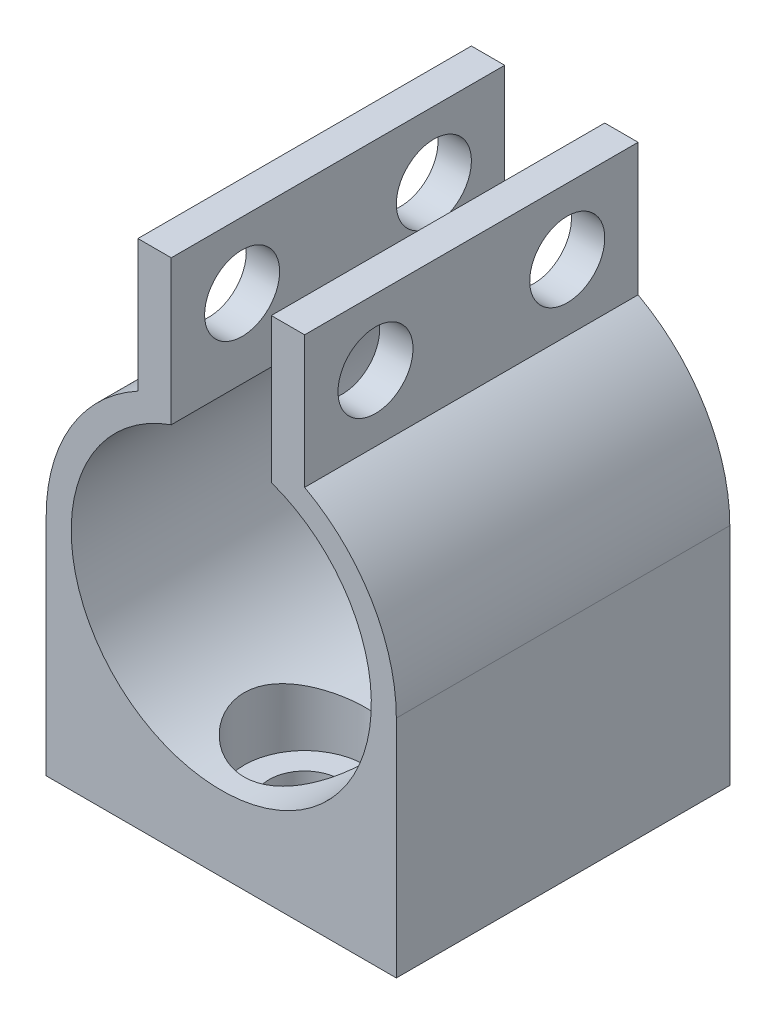
SolidWorks part; units mm, degrees
ref_plane "Front Plane" through (0, 0, 0) normal (0, 0, 1) x (1, 0, 0)
ref_plane "Top Plane" through (0, 0, 0) normal (0, 1, 0) x (1, 0, 0)
ref_plane "Right Plane" through (0, 0, 0) normal (1, 0, 0) x (0, 0, -1)
sketch "Sketch1" plane through (0, 0, 0) normal (0, 0, 1) x (1, 0, 0)
  line L0 (-3, 8.4853) -> (-3, 17.1595)
  line L1 (0, -2.4456) -> (0, 3.9231) construction
  line L2 (-3, 17.1595) -> (-5, 17.1595)
  line L3 (-5, 17.1595) -> (-5, 9.2331)
  line L4 (5, 17.1595) -> (5, 9.2331)
  line L5 (3, 17.1595) -> (5, 17.1595)
  line L6 (3, 8.4853) -> (3, 17.1595)
  line L10 (10.5, -13.5) -> (-10.5, -13.5)
  line L11 (10.5, 0) -> (10.5, -13.5)
  line L12 (-10.5, 0) -> (-10.5, -13.5)
  arc A0 (-3, 8.4853) -> (3, 8.4853) centre (0, 0) ccw
  arc A1 (-5, 9.2331) -> (-10.5, 0) centre (0, 0) ccw
  arc A2 (10.5, 0) -> (5, 9.2331) centre (0, 0) ccw
  point P15 (0, -9)
  point P17 (0, -13.5)
  dimension "D1" = 1.5
  dimension "D2" = 18
  dimension "D3" = 3
  dimension "D4" = 2
  dimension "D5" = 4.5
extrude "Boss-Extrude1" add sketch "Sketch1" along normal blind 20 contours L3 A1 L12 L10 L11 A2 L4 L5 L6 A0 L0 L2
ref_plane "Plane1" through (-5, 9.2331, 20) normal (0, -1, 0) x (-1, 0, 0)
sketch "Sketch3" plane through (5, 0, 0) normal (1, 0, 0) x (0, 0, -1)
  line L0 (0, 17.1595) -> (0, 9.2331) construction
  line L1 (-20, 17.1595) -> (-20, 9.2331) construction
  circle A0 centre (-15.75, 13.1963) radius 2.25
  circle A1 centre (-4.25, 13.1963) radius 2.25
  point P4 (0, 0)
  point P6 (0, 0)
  point P9 (-20, 13.1963)
  dimension "D1" = 4.5
  dimension "D2" = 4.5
  dimension "D3" = 4.25
  dimension "D4" = 4.25
extrude "Cut-Extrude1" cut sketch "Sketch3" against normal through all
sketch "Sketch5" plane through (0, -13.5, 0) normal (0, -1, 0) x (1, 0, 0)
  line L0 (10.5, 0) -> (-10.5, 0) construction
  line L1 (10.5, 20) -> (-10.5, 20) construction
  circle A0 centre (0, 5) radius 2.125
  circle A1 centre (0, 15) radius 2.125
  point P4 (0, 0)
  point P5 (0, 0)
  point P7 (0, 0)
  point P8 (0, 6.4602)
  dimension "D1" = 4.25
  dimension "D2" = 4.25
  dimension "D3" = 5
  dimension "D4" = 5
extrude "Cut-Extrude2" cut sketch "Sketch5" against normal through all
sketch "Sketch6" plane through (0, -13.5, 0) normal (0, -1, 0) x (1, 0, 0)
  circle A0 centre (0, 15) radius 3.625
  circle A1 centre (0, 5) radius 3.625
extrude "Cut-Extrude6" cut sketch "Sketch6" along normal blind 4.5 from offset 6 offset against normal yes
